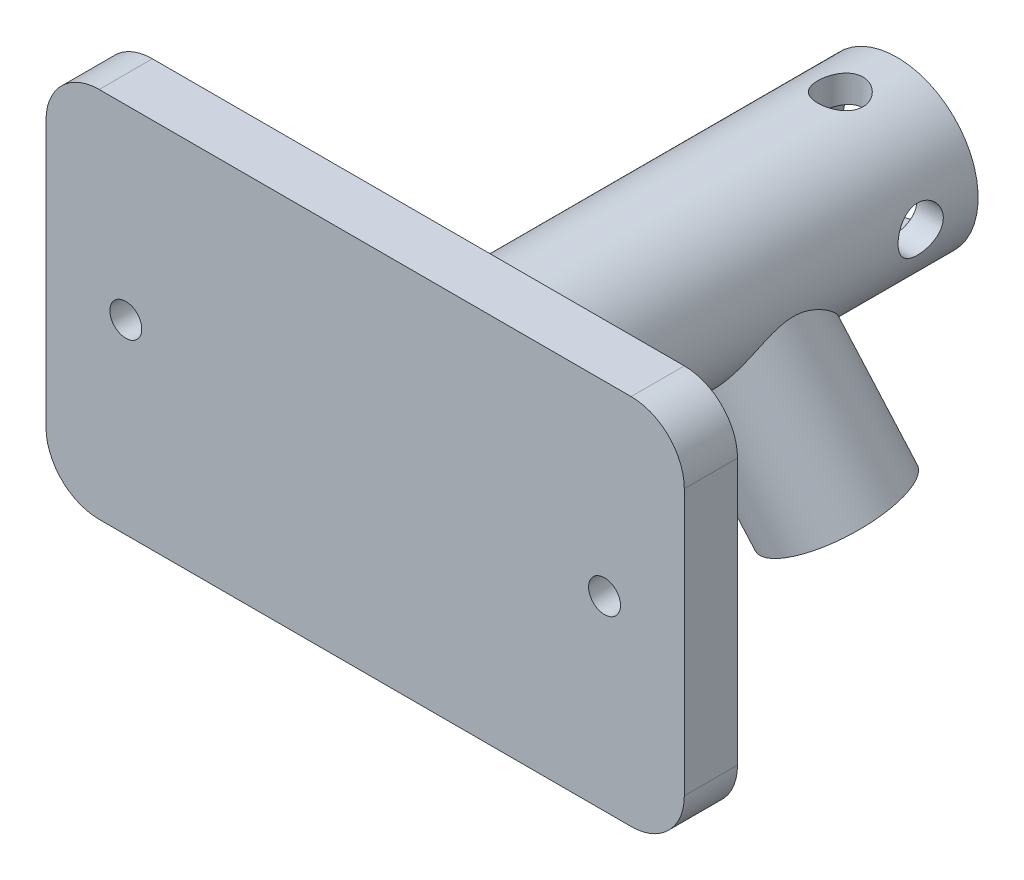
SolidWorks part; units mm, degrees
ref_plane "Front Plane" through (0, 0, 0) normal (0, 0, 1) x (1, 0, 0)
ref_plane "Top Plane" through (0, 0, 0) normal (0, 1, 0) x (1, 0, 0)
ref_plane "Right Plane" through (0, 0, 0) normal (1, 0, 0) x (0, 0, -1)
sketch "Sketch1" plane through (0, 0, 0) normal (0, 0, 1) x (1, 0, 0)
  line L0 (-60, 0) -> (70.8805, 0) construction
  line L1 (-60, -35) -> (60, -35)
  line L2 (-60, -35) -> (-60, 35)
  line L3 (-60, 35) -> (60, 35)
  line L4 (60, -35) -> (60, 35)
  line L5 (-60, -35) -> (60, 35) construction
  line L6 (-60, 35) -> (60, -35) construction
  line L7 (0, 37.935) -> (0, -47.1803) construction
  circle A0 centre (-45, 0) radius 3
  circle A1 centre (45, 0) radius 3
  point P0 (0, 0)
  dimension "D4" = 6
  dimension "D1" = 70
  dimension "D2" = 120
  dimension "D3" = 45
extrude "Boss-Extrude1" add sketch "Sketch1" along normal blind 10
sketch "Sketch2" plane through (0, 0, 0) normal (0, 0, -1) x (-1, 0, 0)
  circle A0 centre (0, 0) radius 15.24
  circle A1 centre (0, 0) radius 10.16
  dimension "D1" = 30.48
  dimension "D2" = 5.08
extrude "Boss-Extrude2" add sketch "Sketch2" along normal blind 90
ref_plane "Plane1" through (12.9986, -24.3403, -4.5288) normal (-0.4649, 0.8705, 0.162) x (0.8854, 0.457, 0.085)
ref_axis "Axis1" through (-24.1897, 45.5408, -45.4371) along (0.4649, -0.8705, -0.162)
sketch "Sketch4" plane through (12.9986, -24.3403, -4.5288) normal (-0.4649, 0.8705, 0.162) x (0.8854, 0.457, 0.085)
  circle A0 centre (-4.4684, 53.001) radius 12.7 construction
  circle A1 centre (-4.4684, 53.001) radius 12.7
  circle A2 centre (-4.4684, 53.001) radius 12.2
  circle A3 centre (-4.4684, 53.001) radius 10.2
  dimension "D1" = 0.5
  dimension "D2" = 2
extrude "Boss-Extrude4" add sketch "Sketch4" along direction (0.4649, -0.8705, -0.162) on the side of the normal blind 27 and the other way blind 20 contours A2 A3 region at (-1.4539, -22.1051, -58.0235)
ref_axis "Axis2" through (0, 0, -90) along (0, 0, 1)
ref_plane "Plane2" through (0, 0, 0) normal (-1, 0, 0) x (0, 0, 1)
sketch "Sketch6" plane through (0, 35, 0) normal (0, 1, 0) x (1, 0, 0)
  circle A0 centre (0, 79.3308) radius 4.25
  dimension "D1" = 8.5
extrude "Cut-Extrude1" cut sketch "Sketch6" against normal blind 58
sketch "Sketch7" plane through (60, 0, 0) normal (1, 0, 0) x (0, 0, -1)
  circle A0 centre (79.1968, 0) radius 4.25
  dimension "D1" = 8.5
extrude "Cut-Extrude2" cut sketch "Sketch7" against normal blind 81
fillet "Fillet1" radius 10 4 edges at (60, -35, 5) (-60, -35, 5) (-60, 35, 5) (60, 35, 5)
sketch "Sketch8" plane through (0, 0, -90) normal (0, 0, -1) x (-1, 0, 0)
  circle A0 centre (0, 0) radius 10.2113
extrude "Cut-Extrude3" cut sketch "Sketch8" against normal blind 81
